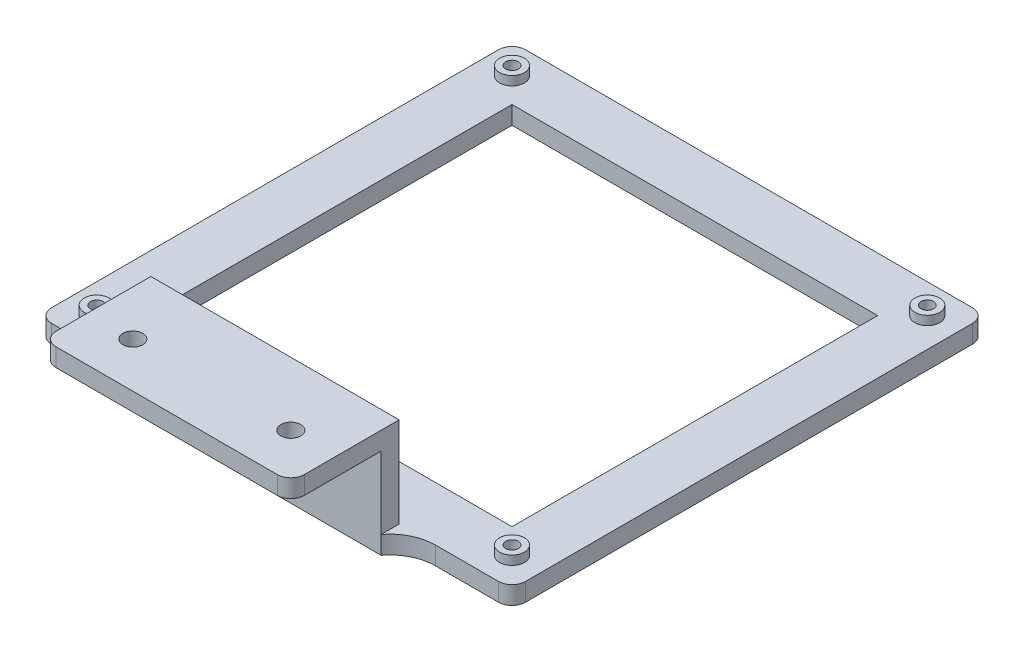
SolidWorks part; units mm, degrees
ref_plane "前视基准面" through (0, 0, 0) normal (0, 0, 1) x (1, 0, 0)
ref_plane "上视基准面" through (0, 0, 0) normal (0, 1, 0) x (1, 0, 0)
ref_plane "右视基准面" through (0, 0, 0) normal (1, 0, 0) x (0, 0, -1)
sketch "草图1" plane through (0, 0, 0) normal (0, 1, 0) x (1, 0, 0)
  line L0 (-75.5116, 0) -> (91.4116, 0) construction
  line L1 (-52.5, 52.5) -> (52.5, 52.5)
  line L2 (-52.5, 52.5) -> (-52.5, -52.5)
  line L3 (-52.5, -52.5) -> (52.5, -52.5)
  line L4 (52.5, 52.5) -> (52.5, -52.5)
  line L5 (-52.5, 52.5) -> (52.5, -52.5) construction
  line L6 (-52.5, -52.5) -> (52.5, 52.5) construction
  line L7 (0, 97.6741) -> (0, -98.8128) construction
  line L8 (-40.5, 40.5) -> (40.5, 40.5)
  line L9 (40.5, 40.5) -> (40.5, -40.5)
  line L10 (-40.5, -40.5) -> (40.5, -40.5)
  line L11 (-40.5, 40.5) -> (-40.5, -40.5)
  circle A0 centre (-46, 46) radius 1.4
  circle A1 centre (-46, -46) radius 1.4
  circle A2 centre (46, -46) radius 1.4
  circle A3 centre (46, 46) radius 1.4
  circle A4 centre (-46, 46) radius 2.75
  circle A5 centre (46, 46) radius 2.75
  circle A6 centre (46, -46) radius 2.75
  circle A7 centre (-46, -46) radius 2.75
  point P0 (0, 0)
  dimension "D6" = 2.8
  dimension "D8" = 5.5
  dimension "D1" = 105
  dimension "D2" = 105
  dimension "D3" = 6.5
  dimension "D4" = 6.5
  dimension "D5" = 92
  dimension "D7" = 12
extrude "凸台-拉伸1" add sketch "草图1" along normal blind 4 contours L4 L1 L2 L3 A5 A4 L11 L8 L9 L10 A6 A7 | A5 A3 | A4 A0 | A7 A1 | A6 A2 region at (0, 0, -51.0151) region at (-48.6722, 0, -46) region at (43.3278, 0, -46) region at (43.3278, 0, 46) region at (-48.6722, 0, 46)
extrude "凸台-拉伸2" add sketch "草图1<4>" along normal blind 2 from vertex contours A4 A0 | A5 A3 | A6 A2 | A7 A1 region at (-48.6722, 0, -46) region at (43.3278, 0, -46) region at (43.3278, 0, 46) region at (-48.6722, 0, 46) starting at point (-52.5, 4, 52.5)
sketch "草图1<4>" plane through (0, 0, 0) normal (0, 1, 0) x (1, 0, 0) same geometry as "草图1"
sketch "草图2" plane through (-52.5, 0, 0) normal (-1, 0, 0) x (0, 0, 1)
  line L0 (52.5, 0) -> (56.5, 0)
  line L1 (56.5, 0) -> (56.5, 20)
  line L2 (56.5, 20) -> (76.5, 20)
  line L3 (52.5, 24) -> (52.5, 0)
  line L4 (76.5, 20) -> (76.5, 24)
  line L5 (76.5, 24) -> (52.5, 24)
  dimension "D1" = 4
  dimension "D2" = 24
  dimension "D3" = 20
  dimension "D4" = 20
extrude "凸台-拉伸3" add sketch "草图2" against normal blind 55 from offset 25 offset against normal yes
sketch "草图3" plane through (0, 24, 0) normal (0, 1, 0) x (1, 0, 0)
  line L0 (27.5, -76.5) -> (-27.5, -76.5) construction
  line L1 (27.5, -76.5) -> (27.5, -52.5) construction
  circle A0 centre (17.5, -66.5) radius 2.2
  circle A1 centre (-17.5, -66.5) radius 2.2
  dimension "D1" = 4.4
  dimension "D2" = 4.4
  dimension "D3" = 10
  dimension "D4" = 10
  dimension "D5" = 35
extrude "切除-拉伸1" cut sketch "草图3" against normal up to next
fillet "圆角1" radius 3 6 edges at (-52.5, 2, -52.5) (52.5, 2, -52.5) (52.5, 2, 52.5) (27.5, 22, 76.5) (-27.5, 22, 76.5) (-52.5, 2, 52.5)
fillet "圆角2" radius 10 2 edges
